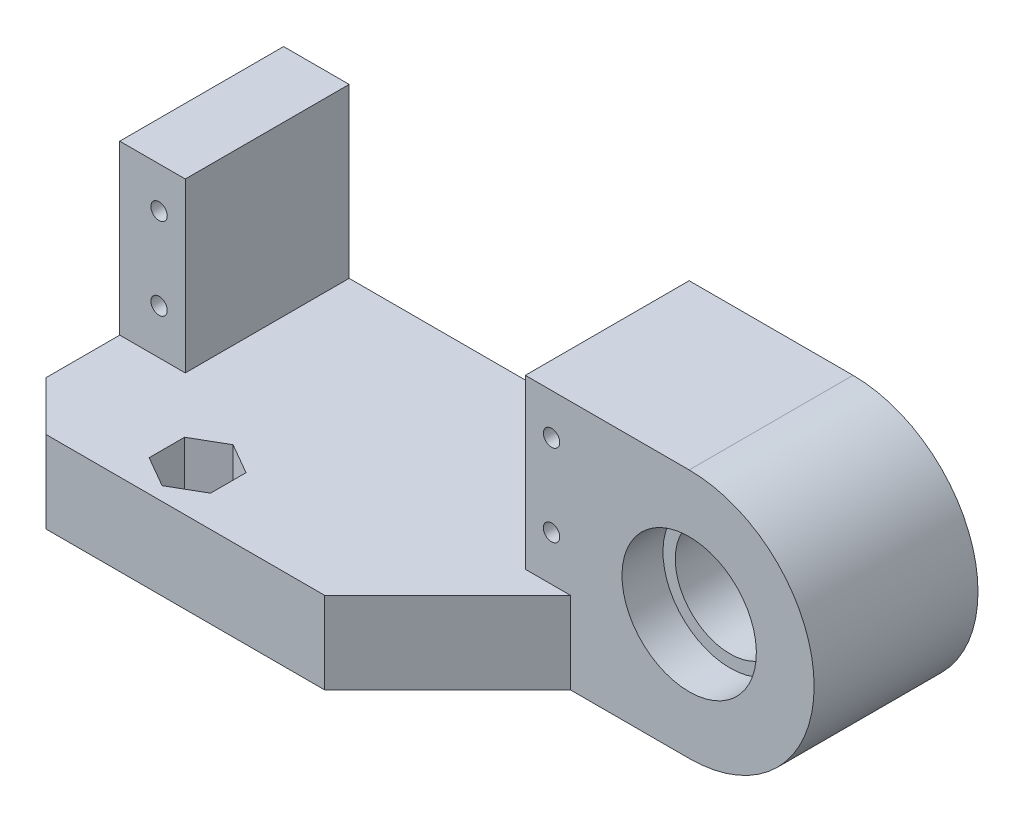
SolidWorks part; units mm, degrees
ref_plane "Front Plane" through (0, 0, 0) normal (0, 0, 1) x (1, 0, 0)
ref_plane "Top Plane" through (0, 0, 0) normal (0, 1, 0) x (1, 0, 0)
ref_plane "Right Plane" through (0, 0, 0) normal (1, 0, 0) x (0, 0, -1)
sketch "Sketch1" plane through (0, 0, 0) normal (0, 0, 1) x (1, 0, 0)
  line L0 (-20, 15.25) -> (0, 15.25)
  line L2 (-61.5, 15.25) -> (-61.5, -5.25)
  line L3 (-61.5, -5.25) -> (-20, -5.25)
  line L4 (-20, 15.25) -> (-20, -5.25)
  line L5 (-69.5, 15.25) -> (-61.5, 15.25)
  line L6 (-69.5, 15.25) -> (-69.5, -15.25)
  line L7 (-69.5, -15.25) -> (0, -15.25)
  line L8 (0, 15.25) -> (0, -15.25) construction
  arc A0 (0, 15.25) -> (0, -15.25) centre (0, 0) cw
  dimension "D1" = 41.5
  dimension "D2" = 20.5
  dimension "D3" = 8
  dimension "D4" = 20
  dimension "D5" = 10
extrude "Boss-Extrude1" add sketch "Sketch1" along normal blind 20
sketch "Sketch4" plane through (0, 0, 0) normal (1, 0, 0) x (0, 0, -1)
  line L0 (-20, 0) -> (0, 0) construction
  line L3 (0, 0) -> (0, 8.2)
  line L4 (0, 8.2) -> (-5, 8.2)
  line L5 (-5, 8.2) -> (-5, 6.7)
  line L6 (-5, 6.7) -> (-15, 6.7)
  line L7 (-15, 6.7) -> (-15, 8.2)
  line L8 (-15, 8.2) -> (-20, 8.2)
  line L10 (-20, 8.2) -> (-20, 0)
  line L11 (-20, 0) -> (0, 0)
  line L14 (0, -15.25) -> (0, 15.25) construction
  line L15 (-20, 15.25) -> (-20, -15.25) construction
  dimension "D1" = 5
  dimension "D2" = 16.4
  dimension "D3" = 1.5
revolve "Cut-Revolve1" cut sketch "Sketch4" angle 360 about L0
sketch "Sketch5" plane through (0, 0, 20) normal (0, 0, 1) x (1, 0, 0)
  line L0 (-20, -5.25) -> (-61.5, -5.25) construction
  line L1 (-69.5, -5.25) -> (-14.5, -5.25)
  line L2 (-69.5, -5.25) -> (-69.5, -15.25)
  line L3 (-69.5, -15.25) -> (-14.5, -15.25)
  line L4 (-14.5, -5.25) -> (-14.5, -15.25)
  line L5 (-69.5, -15.25) -> (0, -15.25) construction
  dimension "D1" = 55
extrude "Boss-Extrude2" add sketch "Sketch5" along normal blind 15
chamfer "Chamfer1" distance 15 angle 45 1 edges at (-14.5, -10.25, 35)
chamfer "Chamfer2" distance 6 angle 45 1 edges at (-69.5, -10.25, 35)
sketch "Sketch6" plane through (0, -15.25, 0) normal (0, -1, 0) x (1, 0, 0)
  line L0 (-69.5, 29) -> (-69.5, 0) construction
  line L1 (-63.5, 35) -> (-29.5, 35) construction
  circle A0 centre (-51, 29) radius 2.25
  dimension "D1" = 4.5
  dimension "D3" = 6
  dimension "D2" = 18.5
extrude "Cut-Extrude1" cut sketch "Sketch6" against normal through all
sketch "Sketch7" plane through (0, -5.25, 0) normal (0, 1, 0) x (1, 0, 0)
  line L1 (-51, -33.3301) -> (-47.25, -31.1651)
  line L2 (-47.25, -31.1651) -> (-47.25, -26.8349)
  line L3 (-47.25, -26.8349) -> (-51, -24.6699)
  line L4 (-51, -24.6699) -> (-54.75, -26.8349)
  line L5 (-54.75, -26.8349) -> (-54.75, -31.1651)
  line L6 (-54.75, -31.1651) -> (-51, -33.3301)
  circle A0 centre (-51, -29) radius 3.75 construction
  dimension "D1" = 7.5
extrude "Cut-Extrude2" cut sketch "Sketch7" against normal blind 6
sketch "Sketch8" plane through (0, 0, 20) normal (0, 0, 1) x (1, 0, 0)
  line L0 (-64.7, 5.25) -> (-61.5, 5.25) construction
  line L1 (-64.7, 10.25) -> (-16.8, 10.25) construction
  line L2 (-64.7, 10.25) -> (-64.7, 0.25) construction
  line L3 (-64.7, 0.25) -> (-16.8, 0.25) construction
  line L4 (-16.8, 10.25) -> (-16.8, 0.25) construction
  line L5 (-61.5, -5.25) -> (-61.5, 15.25) construction
  line L6 (-16.8, 5.25) -> (-20, 5.25) construction
  line L7 (-20, 15.25) -> (-20, -5.25) construction
  line L8 (-61.5, 15.25) -> (-69.5, 15.25) construction
  circle A0 centre (-64.7, 10.25) radius 1
  circle A1 centre (-64.7, 0.25) radius 1
  circle A2 centre (-16.8, 0.25) radius 1
  circle A3 centre (-16.8, 10.25) radius 1
  dimension "D4" = 2
  dimension "D1" = 10
  dimension "D2" = 47.9
  dimension "D3" = 10
extrude "Cut-Extrude3" cut sketch "Sketch8" against normal blind 15
